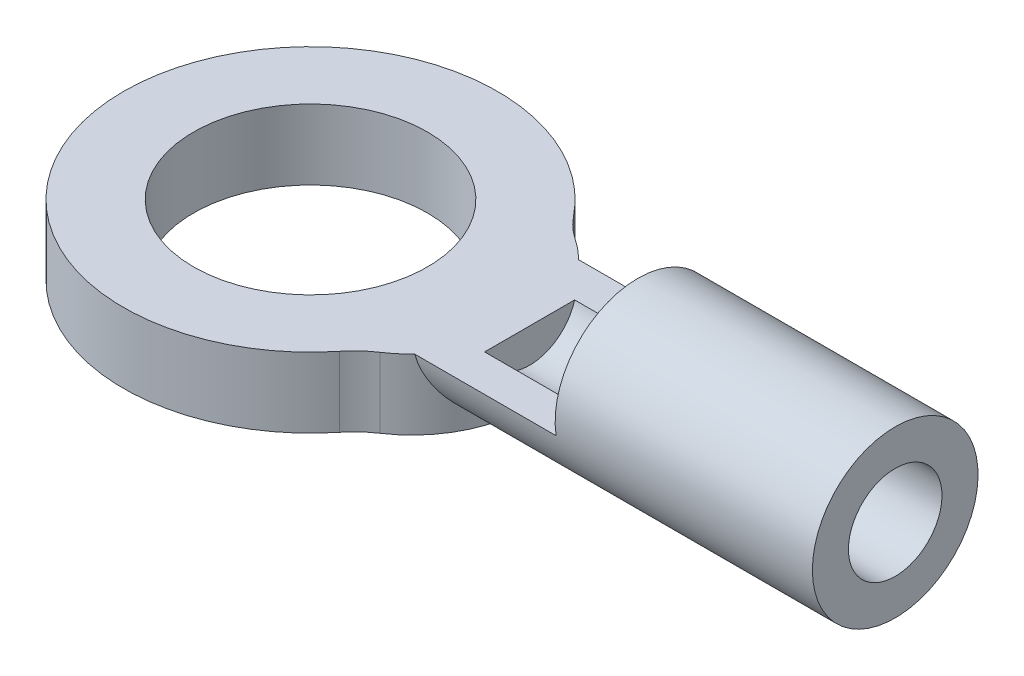
SolidWorks part; units mm, degrees
ref_plane "Front" through (0, 0, 0) normal (0, 0, 1) x (1, 0, 0)
ref_plane "Top" through (0, 0, 0) normal (0, 1, 0) x (1, 0, 0)
ref_plane "Right" through (0, 0, 0) normal (1, 0, 0) x (0, 0, -1)
sketch "Эскиз1" plane through (0, 0, 0) normal (0, 1, 0) x (1, 0, 0)
  line L0 (4.6837, 1.75) -> (12.5, 1.75)
  line L1 (12.5, -1.75) -> (4.6837, -1.75)
  line L2 (12.5, 1.75) -> (12.5, -1.75)
  circle A0 centre (0, 0) radius 2.5
  arc A1 (3.1225, 2.5) -> (3.1225, -2.5) centre (0, 0) ccw
  arc A2 (3.1225, -2.5) -> (4.6837, -1.75) centre (4.6837, -3.75) cw
  arc A3 (3.1225, 2.5) -> (4.6837, 1.75) centre (4.6837, 3.75) ccw
  point P9 (-4, 0)
  dimension "D1" = 5
  dimension "D4" = 4
  dimension "D6" = 2
  dimension "D2" = 1.75
  dimension "D3" = 1.75
  dimension "D5" = 16.5
extrude "Бобышка-Вытянуть1" add sketch "Эскиз1" along normal blind 1.5
sketch "Эскиз2" plane through (0, 0, 0) normal (1, 0, 0) x (0, 0, -1)
  line L4 (-1.75, 0) -> (1.75, 0) construction
  line L5 (-1.75, 1.5) -> (-1.75, 0)
  line L6 (-1.75, 0) -> (1.75, 0)
  line L7 (1.75, 0) -> (1.75, 1.5)
  line L8 (-1.75, 1.5) -> (-0.9626, 1.5)
  line L9 (1.75, 1.5) -> (0.9626, 1.5)
  circle A0 centre (0, 1.7708) radius 1.7708
  circle A1 centre (0, 1.7708) radius 1
  dimension "D2" = 2
extrude "Бобышка-Вытянуть2" add sketch "Эскиз2" against normal blind 5.5 from surface contours A0 A1 | A0 region at (0, 3.4957, 0.1327) starting at face at (12.5, 0.75, 0)
extrude "Вырез-Вытянуть1" cut sketch "Эскиз2<3>" against normal up to vertex (-4.6837 mm away) from surface contours A1 | A0 L5 L6 | A0 L6 L7 region at (0, 0.3748, 1.3553) region at (0, 1.7708, 0) region at (0, 0.3748, -1.3553) up to point (4.6838, 1.5, 1.75) starting at face at (12.5, 1.2604, 0)
sketch "Эскиз2<3>" plane through (0, 0, 0) normal (1, 0, 0) x (0, 0, -1) same geometry as "Эскиз2"
fillet "Скругление1" radius 2.5 2 edges at (4.6837, 0.75, 1.75) (4.6837, 0.75, -1.75)
